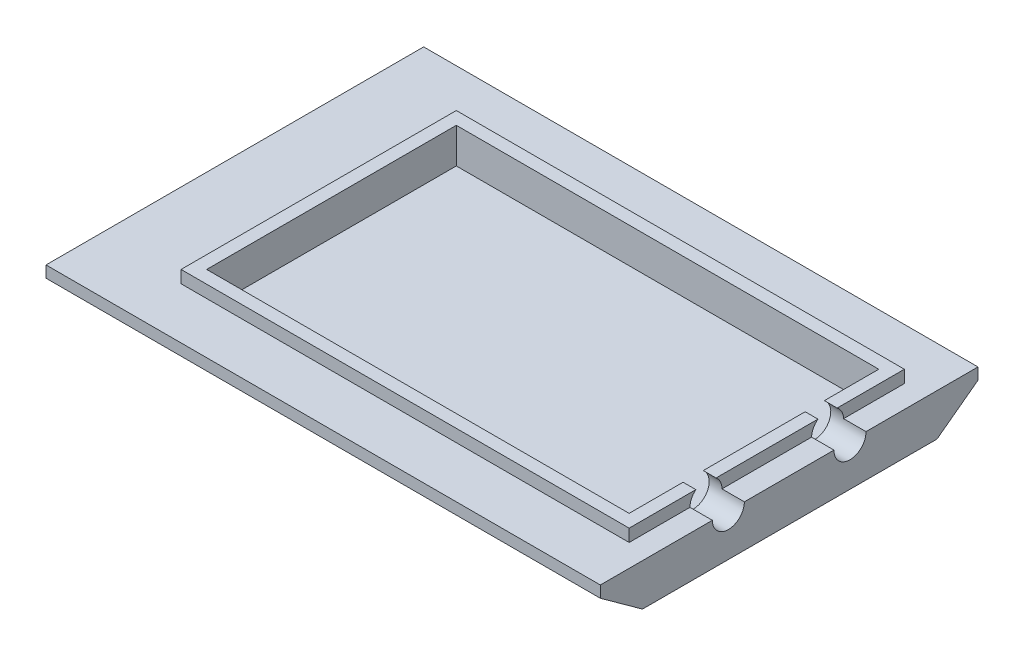
SolidWorks part; units mm, degrees
ref_plane "Front Plane" through (0, 0, 0) normal (0, 0, 1) x (1, 0, 0)
ref_plane "Top Plane" through (0, 0, 0) normal (0, 1, 0) x (1, 0, 0)
ref_plane "Right Plane" through (0, 0, 0) normal (1, 0, 0) x (0, 0, -1)
sketch "Sketch1" plane through (0, 0, 0) normal (0, 1, 0) x (1, 0, 0)
  line L1 (-190.5, 0) -> (0, 0)
  line L2 (-190.5, 0) -> (-190.5, -116.84)
  line L3 (-190.5, -116.84) -> (0, -116.84)
  line L4 (0, 0) -> (0, -116.84)
  dimension "D1" = 190.5
  dimension "D2" = 116.84
ref_plane "Plane1" through (0, 12.0904, 0) normal (0, 1, 0) x (1, 0, 0)
sketch "Sketch2" plane through (0, 12.0904, 0) normal (0, 1, 0) x (1, 0, 0)
  line L0 (0, -6.6497) -> (0, 6.6497) construction
  line L1 (-219.964, 16.2891) -> (0, 16.2891)
  line L2 (-219.964, 16.2891) -> (-219.964, -133.5709)
  line L3 (-219.964, -133.5709) -> (0, -133.5709)
  line L4 (0, 16.2891) -> (0, -133.5709)
  line L5 (-190.5, 0) -> (0, 0) construction
  dimension "D1" = 149.86
  dimension "D2" = 219.964
  dimension "D3" = 16.2891
loft "Loft1" add profiles "Sketch2", "Sketch1" connector at (-219.964, 12.0904, 133.5709) connector at (-190.5, 0, 116.84)
extrude "Boss-Extrude2" add sketch "Sketch2<2>" along normal blind 4.572
sketch "Sketch2<2>" plane through (0, 12.0904, 0) normal (0, 1, 0) x (1, 0, 0) same geometry as "Sketch2"
ref_plane "Plane2" through (0, 16.51, 0) normal (0, 1, 0) x (1, 0, 0)
sketch "Sketch3" plane through (0, 16.51, 0) normal (0, 1, 0) x (1, 0, 0)
  line L0 (0, -133.5709) -> (0, 16.2891) construction
  line L1 (-186.69, -4.0309) -> (-8.89, -4.0309)
  line L2 (-186.69, -4.0309) -> (-186.69, -113.2509)
  line L3 (-186.69, -113.2509) -> (-8.89, -113.2509)
  line L4 (-8.89, -4.0309) -> (-8.89, -113.2509)
  line L5 (-219.964, -133.5709) -> (0, -133.5709) construction
  dimension "D1" = 177.8
  dimension "D2" = 109.22
  dimension "D3" = 8.89
  dimension "D4" = 20.32
extrude "Boss-Extrude3" add sketch "Sketch3" along normal blind 5.08
sketch "Sketch4" plane through (0, 16.51, 0) normal (0, 1, 0) x (1, 0, 0)
  line L0 (-181.61, -9.1109) -> (-181.61, -108.1709)
  line L5 (-181.61, -108.1709) -> (-13.97, -108.1709)
  line L6 (-13.97, -9.1109) -> (-13.97, -108.1709)
  line L7 (-181.61, -9.1109) -> (-13.97, -9.1109)
  line L8 (-8.89, -113.2509) -> (-8.89, -4.0309) construction
  line L9 (-186.69, -4.0309) -> (-186.69, -113.2509) construction
  line L11 (-186.69, -4.0309) -> (-8.89, -4.0309) construction
  line L12 (-186.69, -113.2509) -> (-8.89, -113.2509) construction
  dimension "D1" = 5.08
  dimension "D2" = 5.08
  dimension "D3" = 5.08
  dimension "D4" = 5.08
extrude "Cut-Extrude1" cut sketch "Sketch4" along normal through all
extrude "Cut-Extrude2" cut sketch "Sketch4<2>" against normal blind 8.89
sketch "Sketch4<2>" plane through (0, 16.51, 0) normal (0, 1, 0) x (1, 0, 0) same geometry as "Sketch4"
sketch "Sketch5" plane through (0, 0, 0) normal (1, 0, 0) x (0, 0, -1)
  line L0 (-133.5709, 16.6624) -> (16.2891, 16.6624) construction
  line L1 (82.4231, 16.51) -> (-82.4231, 16.51) construction
  circle A0 centre (-82.7709, 16.6624) radius 6.35
  circle A1 centre (-34.5109, 16.51) radius 6.35
  dimension "D1" = 12.7
  dimension "D3" = 12.7
  dimension "D2" = 50.8
  dimension "D4" = 50.8
extrude "Cut-Extrude3" cut sketch "Sketch5" against normal blind 19.05
